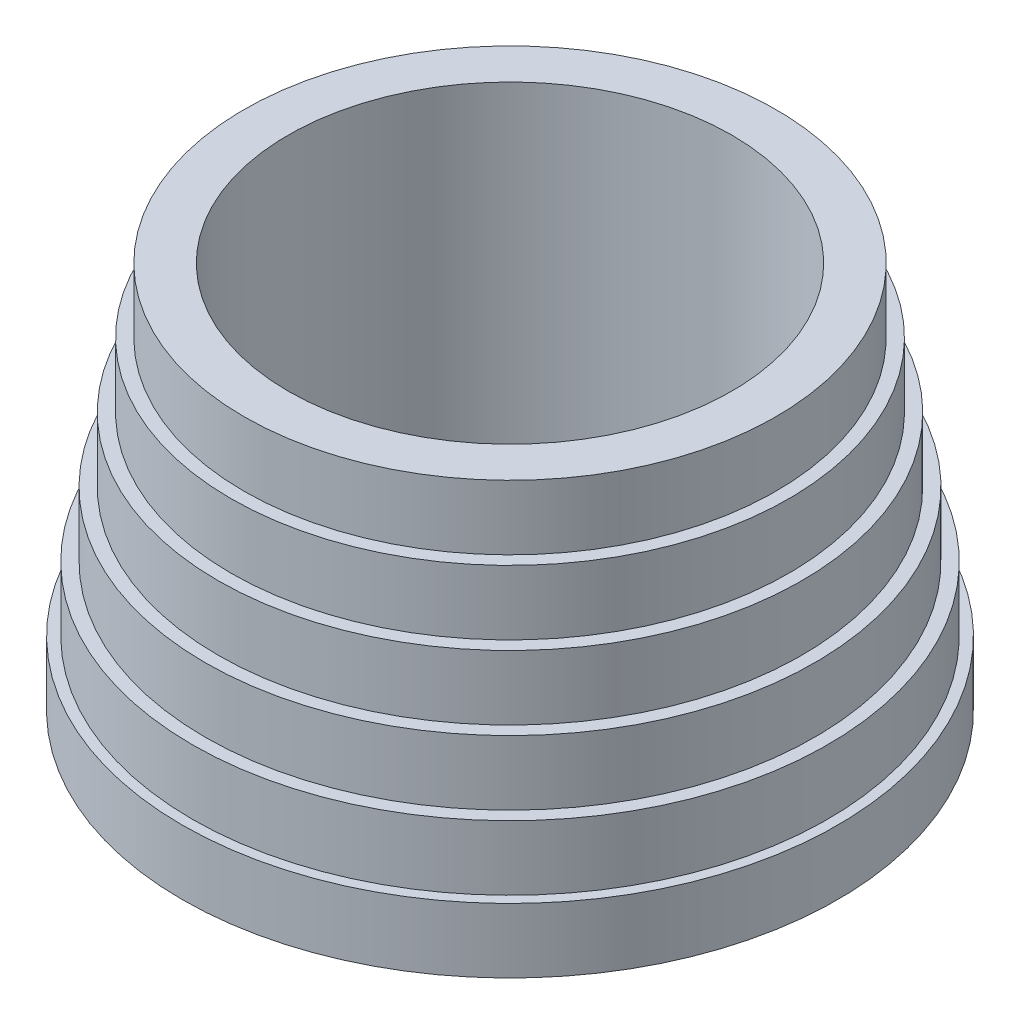
SolidWorks part; units mm, degrees
ref_plane "Front Plane" through (0, 0, 0) normal (0, 0, 1) x (1, 0, 0)
ref_plane "Top Plane" through (0, 0, 0) normal (0, 1, 0) x (1, 0, 0)
ref_plane "Right Plane" through (0, 0, 0) normal (1, 0, 0) x (0, 0, -1)
sketch "Sketch4" plane through (0, 0, 0) normal (0, 0, 1) x (1, 0, 0)
  line L0 (0, 105.4944) -> (0, -194.5056) construction
  line L1 (-253.7753, -190) -> (-245.9942, -190)
  line L2 (-253.7753, -190) -> (-253.7753, -140)
  line L3 (-253.7753, -140) -> (-245.9942, -140)
  line L4 (-245.9942, -140) -> (-245.9942, -90)
  line L5 (-245.9942, -90) -> (-235.9942, -90)
  line L6 (-235.9942, -90) -> (-235.9942, -40)
  line L7 (-235.9942, -40) -> (-225.9942, -40)
  line L8 (-225.9942, -40) -> (-225.9942, 10)
  line L9 (-225.9942, 10) -> (-215.9942, 10)
  line L10 (-215.9942, 10) -> (-215.9942, 60)
  line L11 (-215.9942, 60) -> (-205.9942, 60)
  line L12 (-205.9942, 60) -> (-205.9942, 110)
  line L13 (-205.9942, 110) -> (-195.9942, 110)
  line L14 (-195.9942, 110) -> (-195.9942, 50)
  line L15 (-245.9942, -190) -> (-245.9942, -150)
  line L16 (-245.9942, -150) -> (-235.9942, -150)
  line L17 (-235.9942, -150) -> (-235.9942, -100)
  line L18 (-235.9942, -100) -> (-225.9942, -100)
  line L19 (-225.9942, -100) -> (-225.9942, -50)
  line L20 (-225.9942, -50) -> (-215.9942, -50)
  line L21 (-215.9942, -50) -> (-215.9942, 0)
  line L22 (-215.9942, 0) -> (-205.9942, 0)
  line L23 (-205.9942, 0) -> (-205.9942, 50)
  line L24 (-205.9942, 50) -> (-195.9942, 50)
  dimension "D1" = 300
  dimension "D2" = 7.7811
  dimension "D3" = 50
  dimension "D4" = 50
  dimension "D5" = 10
  dimension "D6" = 50
  dimension "D7" = 10
  dimension "D8" = 50
  dimension "D9" = 10
  dimension "D10" = 50
  dimension "D11" = 10
  dimension "D12" = 50
  dimension "D13" = 10
  dimension "D14" = 60
  dimension "D15" = 10
  dimension "D16" = 50
  dimension "D17" = 10
  dimension "D18" = 50
  dimension "D19" = 10
  dimension "D20" = 50
  dimension "D21" = 10
  dimension "D22" = 50
  dimension "D23" = 10
revolve "Revolve3" add sketch "Sketch4" angle 360 about L0
sketch "Sketch9" plane through (0, 110, 0) normal (0, 1, 0) x (1, 0, 0)
  circle A0 centre (0, 0) radius 195.9942
  circle A1 centre (0, 0) radius 171.7791
extrude "Boss-Extrude1" add sketch "Sketch9" against normal blind 280.9855
chamfer "Chamfer1" distance 10 angle 45 1 edges at (0, -170.9855, 195.9942)
